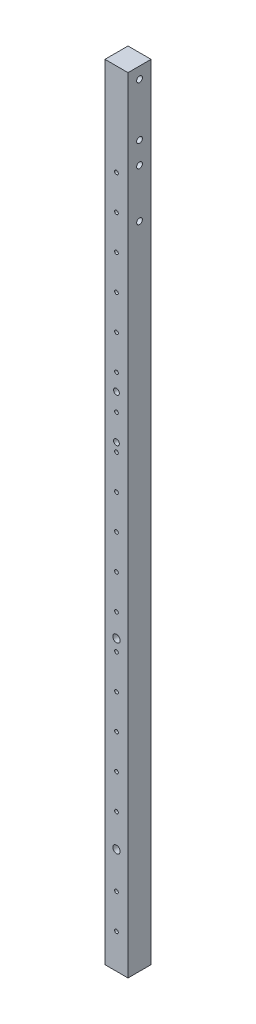
SolidWorks part; units mm, degrees
material "Alliage 1060"
ref_plane "Plan de face" through (0, 0, 0) normal (0, 0, 1) x (1, 0, 0)
ref_plane "Plan de dessus" through (0, 0, 0) normal (0, 1, 0) x (1, 0, 0)
ref_plane "Plan de droite" through (0, 0, 0) normal (1, 0, 0) x (0, 0, -1)
sketch "Esquisse1" plane through (0, 0, 0) normal (0, 1, 0) x (1, 0, 0)
  line L0 (-5, 5) -> (5, -5) construction
  line L1 (-5, 5) -> (5, 5)
  line L2 (-5, 5) -> (-5, -5)
  line L3 (-5, -5) -> (5, -5)
  line L4 (5, 5) -> (5, -5)
  dimension "D1" = 10
extrude "Boss.-Extru.1" add sketch "Esquisse1" along normal up to surface (340 mm away)
hole_wizard "Trou taraudé M3x0.51" positions "Esquisse2" profile "Esquisse3" tap size "M3x0.5" standard "Ansi Metric" end condition through all
sketch "Esquisse2" plane through (-5, 0, 0) normal (-1, 0, 0) x (0, 0, 1)
  line L0 (1.5475, 281.7) -> (-1.5475, 281.7) construction
  line L3 (-1.5475, 302.7) -> (1.5475, 302.7) construction
  point P41 (0, 335)
  point P44 (0, 312.2)
  point P47 (0, 302.7)
  point P49 (0, 281.7)
sketch "Esquisse3" plane through (-5, 335, 0) normal (0, 1, 0) x (0, 0, 1)
  line L0 (0, 0) -> (0, 10)
  line L1 (0, 10) -> (1.25, 10)
  line L2 (1.25, 10) -> (1.25, 0)
  line L5 (1.25, 0) -> (0, 0)
  line L11 (0, -6.35) -> (0, 107.95) construction
  dimension "Diamètre du trou pour taraudage jusqu'au prochain" = 2.5
  dimension "Profondeur du trou pour taraudage jusqu'au prochain" = 10
cosmetic thread "Filetage de perçage1" parameters "D2"=3
cosmetic thread "Filetage de perçage2" parameters "D2"=3
cosmetic thread "Filetage de perçage3" parameters "D2"=3
cosmetic thread "Filetage de perçage4" parameters "D2"=3
hole_wizard "Trou taraudé M2x0.41" positions "Esquisse4" profile "Esquisse5" tap size "M2x0.4" standard "Ansi Metric"
sketch "Esquisse4" plane through (0, 0, 5) normal (0, 0, 1) x (1, 0, 0)
  point P3 (0, 15)
  point P6 (0, 30)
  point P9 (0, 45)
  point P12 (0, 60)
  point P15 (0, 75)
  point P18 (0, 90)
  point P21 (0, 105)
  point P24 (0, 120)
  point P27 (0, 135)
  point P30 (0, 150)
  point P33 (0, 165)
  point P36 (0, 180)
  point P39 (0, 195)
  point P42 (0, 210)
  point P45 (0, 225)
  point P48 (0, 240)
  point P51 (0, 255)
  point P54 (0, 285)
  point P57 (0, 270)
  point P61 (0, 300)
sketch "Esquisse5" plane through (0, 15, 5) normal (1, 0, 0) x (0, -1, 0)
  line L0 (0, 0) -> (0, 6)
  line L1 (0, 6) -> (0.8, 6)
  line L2 (0.8, 6) -> (0.8, 0)
  line L5 (0.8, 0) -> (0, 0)
  line L10 (0, 6) -> (-0.8, 6) construction
  line L11 (0, -6.35) -> (0, 107.95) construction
  dimension "Diamètre du trou pour taraudage" = 1.6
  dimension "Profondeur du trou pour taraudage" = 6
  dimension "Angle de pointe" = 180
cosmetic thread "Filetage de perçage5" parameters "D1"=4, "D2"=2
cosmetic thread "Filetage de perçage6" parameters "D1"=4, "D2"=2
cosmetic thread "Filetage de perçage7" parameters "D1"=4, "D2"=2
cosmetic thread "Filetage de perçage8" parameters "D1"=4, "D2"=2
cosmetic thread "Filetage de perçage9" parameters "D1"=4, "D2"=2
cosmetic thread "Filetage de perçage10" parameters "D1"=4, "D2"=2
cosmetic thread "Filetage de perçage11" parameters "D1"=4, "D2"=2
cosmetic thread "Filetage de perçage12" parameters "D1"=4, "D2"=2
cosmetic thread "Filetage de perçage13" parameters "D1"=4, "D2"=2
cosmetic thread "Filetage de perçage14" parameters "D1"=4, "D2"=2
cosmetic thread "Filetage de perçage15" parameters "D1"=4, "D2"=2
cosmetic thread "Filetage de perçage16" parameters "D1"=4, "D2"=2
cosmetic thread "Filetage de perçage17" parameters "D1"=4, "D2"=2
cosmetic thread "Filetage de perçage18" parameters "D1"=4, "D2"=2
cosmetic thread "Filetage de perçage19" parameters "D1"=4, "D2"=2
cosmetic thread "Filetage de perçage20" parameters "D1"=4, "D2"=2
cosmetic thread "Filetage de perçage21" parameters "D1"=4, "D2"=2
cosmetic thread "Filetage de perçage22" parameters "D1"=4, "D2"=2
cosmetic thread "Filetage de perçage23" parameters "D1"=4, "D2"=2
cosmetic thread "Filetage de perçage25" parameters "D1"=4, "D2"=2
hole_wizard "Trou taraudé M3x0.52" positions "Esquisse6" profile "Esquisse7" tap size "M3x0.5" standard "Ansi Metric" end condition through all
sketch "Esquisse6" plane through (0, 0, -5) normal (0, 0, -1) x (-1, 0, 0)
  point P0 (0, 217.7)
  point P3 (0, 198.7)
sketch "Esquisse7" plane through (0, 217.7, -5) normal (1, 0, 0) x (0, 1, 0)
  line L0 (0, 0) -> (0, 10)
  line L1 (0, 10) -> (1.25, 10)
  line L2 (1.25, 10) -> (1.25, 0)
  line L5 (1.25, 0) -> (0, 0)
  line L11 (0, -6.35) -> (0, 107.95) construction
  dimension "Diamètre du trou pour taraudage jusqu'au prochain" = 2.5
  dimension "Profondeur du trou pour taraudage jusqu'au prochain" = 10
cosmetic thread "Filetage de perçage26" parameters "D2"=3
cosmetic thread "Filetage de perçage27" parameters "D2"=3
hole_wizard "Trou taraudé M3x0.53" positions "Esquisse8" profile "Esquisse9" tap size "M3x0.5" standard "Ansi Metric"
sketch "Esquisse8" plane through (0, 0, 0) normal (0, -1, 0) x (-1, 0, 0)
  point P0 (0, 0)
sketch "Esquisse9" plane through (0, 0, 0) normal (1, 0, 0) x (0, 0, -1)
  line L0 (0, 0) -> (0, 8.5)
  line L1 (0, 8.5) -> (1.25, 8.5)
  line L2 (1.25, 8.5) -> (1.25, 0)
  line L5 (1.25, 0) -> (0, 0)
  line L10 (0, 8.5) -> (-1.25, 8.5) construction
  line L11 (0, -6.35) -> (0, 107.95) construction
  dimension "Diamètre du trou pour taraudage" = 2.5
  dimension "Profondeur du trou pour taraudage" = 8.5
  dimension "Angle de pointe" = 180
cosmetic thread "Filetage de perçage28" parameters "D1"=6, "D2"=3
sketch "Esquisse12" plane through (0, 0, -5) normal (0, 0, -1) x (-1, 0, 0)
  circle A0 centre (0, 125) radius 1.6
  circle A1 centre (0, 45.8) radius 1.6
  dimension "D1" = 3.2
extrude "Enlèv. mat.-Extru.2" cut sketch "Esquisse12" against normal through all
